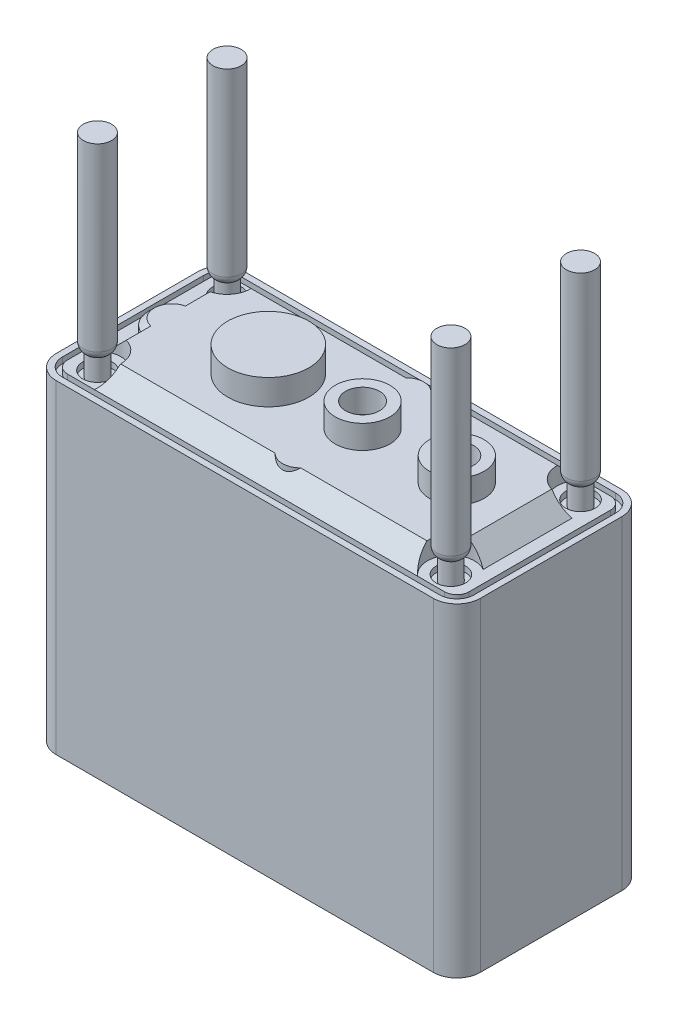
SolidWorks part; units mm, degrees
ref_plane "Front Plane" through (0, 0, 0) normal (0, 0, 1) x (1, 0, 0)
ref_plane "Top Plane" through (0, 0, 0) normal (0, 1, 0) x (1, 0, 0)
ref_plane "Right Plane" through (0, 0, 0) normal (1, 0, 0) x (0, 0, -1)
sketch "Sketch1" plane through (0, 0, 0) normal (0, 1, 0) x (1, 0, 0)
  line L1 (-28.575, 12.7) -> (28.575, 12.7)
  line L2 (-28.575, 12.7) -> (-28.575, -12.7)
  line L3 (-28.575, -12.7) -> (28.575, -12.7)
  line L4 (28.575, 12.7) -> (28.575, -12.7)
  line L5 (-28.575, 12.7) -> (28.575, -12.7) construction
  line L6 (-28.575, -12.7) -> (28.575, 12.7) construction
  point P0 (0, 0)
  dimension "D1" = 57.15
  dimension "D2" = 25.4
extrude "Boss-Extrude1" add sketch "Sketch1" along normal blind 43.6562
fillet "Fillet1" radius 3.175 4 edges at (-28.575, 21.8281, -12.7) (-28.575, 21.8281, 12.7) (28.575, 21.8281, -12.7) (28.575, 21.8281, 12.7)
sketch "Sketch2" plane through (0, 43.6562, 0) normal (0, 1, 0) x (1, 0, 0)
  line L8 (25.4, 11.8745) -> (-25.4, 11.8745)
  line L9 (-27.7495, 9.525) -> (-27.7495, -9.525)
  line L10 (-25.4, -11.8745) -> (25.4, -11.8745)
  line L11 (27.7495, -9.525) -> (27.7495, 9.525)
  line L12 (25.4, 11.8745) -> (-25.4, 11.8745)
  line L13 (-27.7495, 9.525) -> (-27.7495, -9.525)
  line L14 (-25.4, -11.8745) -> (25.4, -11.8745)
  line L15 (27.7495, -9.525) -> (27.7495, 9.525)
  line L20 (25.4, 11.176) -> (-25.4, 11.176)
  line L21 (-27.051, 9.525) -> (-27.051, -9.525)
  line L22 (-25.4, -11.176) -> (25.4, -11.176)
  line L23 (27.051, -9.525) -> (27.051, 9.525)
  line L24 (25.4, 11.176) -> (-25.4, 11.176)
  line L25 (-27.051, 9.525) -> (-27.051, -9.525)
  line L26 (-25.4, -11.176) -> (25.4, -11.176)
  line L27 (27.051, -9.525) -> (27.051, 9.525)
  arc A8 (-25.4, 11.8745) -> (-27.7495, 9.525) centre (-25.4, 9.525) ccw
  arc A9 (-27.7495, -9.525) -> (-25.4, -11.8745) centre (-25.4, -9.525) ccw
  arc A10 (25.4, -11.8745) -> (27.7495, -9.525) centre (25.4, -9.525) ccw
  arc A11 (27.7495, 9.525) -> (25.4, 11.8745) centre (25.4, 9.525) ccw
  arc A12 (-25.4, 11.8745) -> (-27.7495, 9.525) centre (-25.4, 9.525) ccw
  arc A13 (-27.7495, -9.525) -> (-25.4, -11.8745) centre (-25.4, -9.525) ccw
  arc A14 (25.4, -11.8745) -> (27.7495, -9.525) centre (25.4, -9.525) ccw
  arc A15 (27.7495, 9.525) -> (25.4, 11.8745) centre (25.4, 9.525) ccw
  arc A20 (-25.4, 11.176) -> (-27.051, 9.525) centre (-25.4, 9.525) ccw
  arc A21 (-27.051, -9.525) -> (-25.4, -11.176) centre (-25.4, -9.525) ccw
  arc A22 (25.4, -11.176) -> (27.051, -9.525) centre (25.4, -9.525) ccw
  arc A23 (27.051, 9.525) -> (25.4, 11.176) centre (25.4, 9.525) ccw
  arc A24 (-25.4, 11.176) -> (-27.051, 9.525) centre (-25.4, 9.525) ccw
  arc A25 (-27.051, -9.525) -> (-25.4, -11.176) centre (-25.4, -9.525) ccw
  arc A26 (25.4, -11.176) -> (27.051, -9.525) centre (25.4, -9.525) ccw
  arc A27 (27.051, 9.525) -> (25.4, 11.176) centre (25.4, 9.525) ccw
  dimension "D1" = 0.8255
  dimension "D2" = 1.524
extrude "Cut-Extrude1" cut sketch "Sketch2" against normal blind 0.7937
sketch "Sketch3" plane through (0, 43.6562, 0) normal (0, 1, 0) x (1, 0, 0)
  line L1 (23.8125, -8.7312) -> (-23.8125, -8.7313) construction
  line L2 (23.8125, -8.7312) -> (23.8125, 8.7313) construction
  line L3 (23.8125, 8.7313) -> (-23.8125, 8.7312) construction
  line L4 (-23.8125, -8.7313) -> (-23.8125, 8.7312) construction
  line L5 (23.8125, -8.7312) -> (-23.8125, 8.7312) construction
  line L6 (23.8125, 8.7313) -> (-23.8125, -8.7313) construction
  circle A0 centre (-23.8125, 8.7312) radius 1.9844
  circle A1 centre (-23.8125, -8.7313) radius 1.9844
  circle A2 centre (23.8125, -8.7312) radius 1.9844
  circle A3 centre (23.8125, 8.7313) radius 1.9844
  point P0 (0, 0)
  dimension "D1" = 3.9688
  dimension "D2" = 47.625
  dimension "D3" = 17.4625
extrude "Cut-Extrude2" cut sketch "Sketch3" against normal up to surface (0.7937 mm away) up to face at (0, 42.8625, 0)
sketch "Sketch4" plane through (0, 43.6562, 0) normal (0, 1, 0) x (1, 0, 0)
  line L1 (21.7867, -11.176) -> (-21.7867, -11.176)
  line L2 (25.4, -5.9816) -> (25.4, 5.9816)
  line L3 (21.7867, 11.176) -> (-21.7867, 11.176)
  line L4 (-25.4, -5.9816) -> (-25.4, 5.9816)
  line L5 (-25.4, -11.176) -> (25.4, -11.176) construction
  line L7 (25.4, 11.176) -> (-25.4, 11.176) construction
  arc A0 (-25.4, 5.9816) -> (-21.7867, 11.176) centre (-23.8125, 8.7312) ccw
  arc A1 (-21.7867, -11.176) -> (-25.4, -5.9816) centre (-23.8125, -8.7313) ccw
  arc A2 (25.4, -5.9816) -> (21.7867, -11.176) centre (23.8125, -8.7312) ccw
  arc A3 (21.7867, 11.176) -> (25.4, 5.9816) centre (23.8125, 8.7313) ccw
  point P0 (0, 0)
  dimension "D2" = 6.35
  dimension "D3" = 50.8
extrude "Boss-Extrude2" add sketch "Sketch4" along normal blind 2.3813
chamfer "Chamfer1" distance 2.3813 angle 45 4 edges at (25.4, 46.0375, 0) (0, 46.0375, -11.176) (-25.4, 46.0375, 0) (0, 46.0375, 11.176)
sketch "Sketch5" plane through (0, 46.0375, 0) normal (0, 1, 0) x (1, 0, 0)
  line L0 (-28.575, 9.525) -> (-28.575, -9.525) construction
  line L1 (1.905, -7.1437) -> (1.905, 0) construction
  line L2 (1.905, 0) -> (1.905, 7.1437) construction
  line L3 (-23.0187, 5.6571) -> (-23.0187, -5.6571) construction
  circle A0 centre (1.905, 7.1437) radius 2.3813
  circle A1 centre (1.905, -7.1437) radius 2.3813
  circle A2 centre (-22.5107, 0) radius 3.175
  dimension "D2" = 4.7625
  dimension "D4" = 6.35
  dimension "D1" = 30.48
  dimension "D3" = 7.1437
  dimension "D5" = 0.508
extrude "Boss-Extrude3" add sketch "Sketch5" against normal up to surface (2.3813 mm away) up to face at (-23.8125, 43.6562, -6.7469)
chamfer "Chamfer2" distance 0.7937 angle 45 1 edges at (-25.6857, 46.0375, 0)
sketch "Sketch6" plane through (0, 46.0375, 0) normal (0, 1, 0) x (1, 0, 0)
  line L0 (-9.525, 0) -> (3.175, 0) construction
  line L1 (3.175, 0) -> (15.875, 0) construction
  line L2 (28.575, -9.525) -> (28.575, 9.525) construction
  circle A0 centre (3.175, 0) radius 3.683
  circle A1 centre (3.175, 0) radius 2.286
  circle A2 centre (15.875, 0) radius 3.683
  circle A3 centre (15.875, 0) radius 2.286
  circle A4 centre (-9.525, 0) radius 5.461 construction
  dimension "D1" = 10.922
  dimension "D3" = 7.366
  dimension "D4" = 4.572
  dimension "D2" = 12.7
  dimension "D5" = 12.7
extrude "Boss-Extrude4" add sketch "Sketch6" along normal blind 3.175
sketch "Sketch7" plane through (0, 46.0375, 0) normal (0, 1, 0) x (1, 0, 0)
  circle A0 centre (-9.525, 0) radius 5.461 construction
  circle A1 centre (-9.525, 0) radius 5.461
extrude "Boss-Extrude5" add sketch "Sketch7" along normal blind 3.429
sketch "Sketch8" plane through (0, 42.8625, 0) normal (0, 1, 0) x (1, 0, 0)
  circle A0 centre (-23.8125, -8.7313) radius 1.27
  circle A1 centre (23.8125, -8.7312) radius 1.27
  circle A2 centre (23.8125, 8.7313) radius 1.27
  circle A3 centre (-23.8125, 8.7312) radius 1.27
  dimension "D1" = 2.54
extrude "Boss-Extrude6" add sketch "Sketch8" along normal blind 3.175
sketch "Sketch9" plane through (0, 46.0375, 0) normal (0, 1, 0) x (1, 0, 0)
  circle A0 centre (-23.8125, -8.7313) radius 1.905
  circle A1 centre (-23.8125, 8.7312) radius 1.905
  circle A2 centre (23.8125, 8.7313) radius 1.905
  circle A3 centre (23.8125, -8.7312) radius 1.905
  dimension "D1" = 3.81
extrude "Boss-Extrude7" add sketch "Sketch9" along normal blind 25.4
fillet "Fillet2" radius 1.27 4 edges at (-23.8125, 46.0375, -6.8262) (23.8125, 46.0375, -6.8263) (23.8125, 46.0375, 10.6362) (-23.8125, 46.0375, 10.6363)
